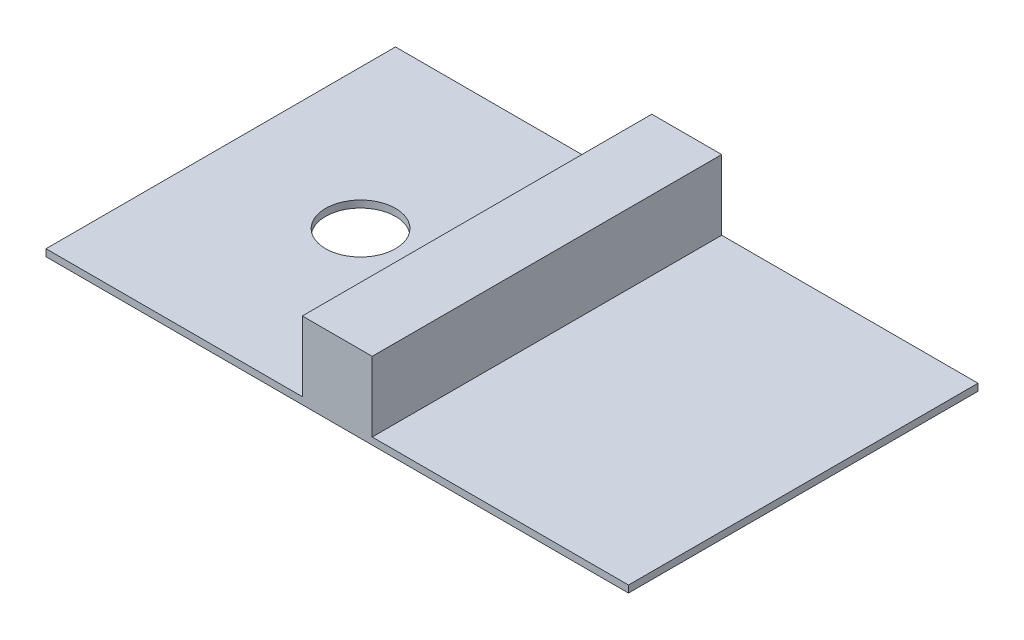
SolidWorks part; units mm, degrees
ref_plane "Front Plane" through (0, 0, 0) normal (0, 0, 1) x (1, 0, 0)
ref_plane "Top Plane" through (0, 0, 0) normal (0, 1, 0) x (1, 0, 0)
ref_plane "Right Plane" through (0, 0, 0) normal (1, 0, 0) x (0, 0, -1)
sketch "Sketch1" plane through (0, 0, 0) normal (0, 1, 0) x (1, 0, 0)
  line L1 (0, 0) -> (25, 0)
  line L2 (0, 0) -> (0, 15)
  line L3 (0, 15) -> (25, 15)
  line L4 (25, 0) -> (25, 15)
extrude "Boss-Extrude1" add sketch "Sketch1" along normal blind 0.3
sketch "Sketch2" plane through (0, 0.3, 0) normal (0, 1, 0) x (1, 0, 0)
  line L0 (25, 15) -> (0, 15) construction
  line L1 (11, 15) -> (14, 15)
  line L2 (11, 15) -> (11, 0)
  line L3 (11, 0) -> (14, 0)
  line L4 (14, 15) -> (14, 0)
  line L5 (0, 0) -> (25, 0) construction
  line L6 (25, 0) -> (25, 15) construction
  line L7 (0, 15) -> (0, 0) construction
  circle A0 centre (6, 7.5) radius 1.5
  line M6 (0, 0) -> (25, 0)
  line M8 (25, 15) -> (0, 15)
  dimension "D5" = 3
  dimension "D1" = 11
  dimension "D2" = 11
  dimension "D3" = 3
  dimension "D4" = 8
extrude "Boss-Extrude2" add sketch "Sketch2" along normal blind 3 contours L4 L2 M8 M6 region at (12.5, 0.3, -7.5)
extrude "Cut-Extrude1" cut sketch "Sketch2<5>" against normal blind 3 contours A0
sketch "Sketch2<5>" plane through (0, 0.3, 0) normal (0, 1, 0) x (1, 0, 0) same geometry as "Sketch2"
